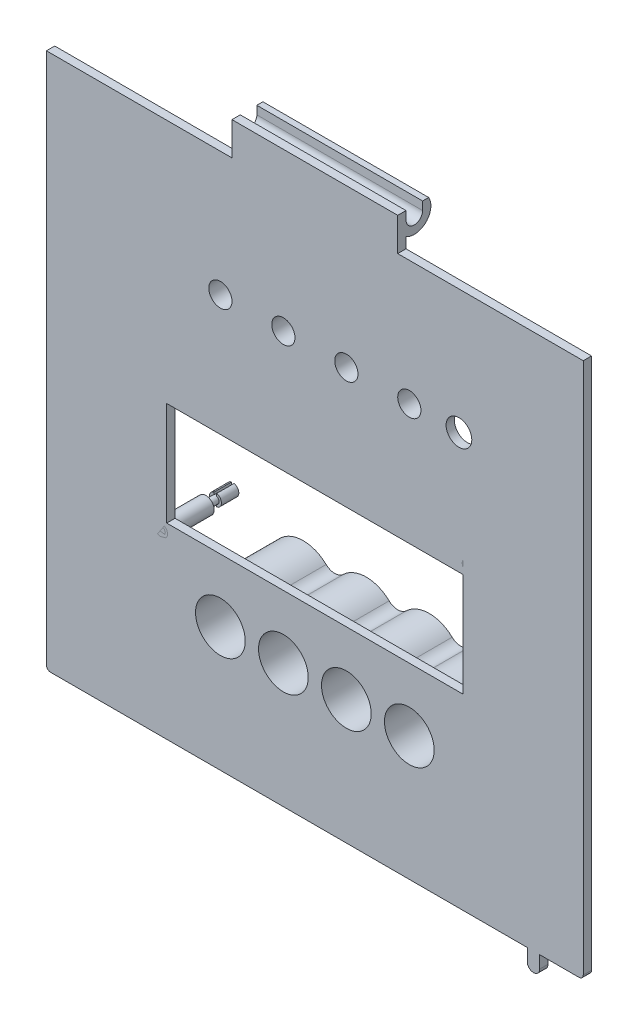
SolidWorks part; units mm, degrees
note: The reader was unsure of these and kept them because the rebuilt part matched: shared geometry of "Sketch1<5>", "Sketch1<6>", "Sketch1<7>", "Sketch1<8>", "Sketch1<9>", "Sketch4<4>", "Sketch4<5>".
ref_plane "Alzado" through (0, 0, 0) normal (0, 0, 1) x (1, 0, 0)
ref_plane "Planta" through (0, 0, 0) normal (0, 1, 0) x (1, 0, 0)
ref_plane "Vista lateral" through (0, 0, 0) normal (1, 0, 0) x (0, 0, -1)
sketch "Sketch1" plane through (0, 0, 0) normal (0, 0, 1) x (1, 0, 0)
  line L1 (-64.775, 64.7) -> (64.775, 64.7)
  line L2 (-64.775, 64.7) -> (-64.775, -64.7)
  line L3 (-64.775, -64.7) -> (51.275, -64.7)
  line L4 (64.775, 64.7) -> (64.775, -64.7)
  line L5 (-64.775, 64.7) -> (64.775, -64.7) construction
  line L6 (-64.775, -64.7) -> (64.775, 64.7) construction
  line L7 (36.7, 9.2186) -> (36.7, 6.3814)
  line L8 (37.3, 9.2186) -> (37.3, 6.3814)
  line L11 (36.7, -20.2814) -> (36.7, -23.1186)
  line L12 (0, 64.7) -> (0, -64.7) construction
  line L13 (37.3, -20.2814) -> (37.3, -23.1186)
  line L14 (-22.8, -34.7) -> (22.8, -34.7) construction
  line L15 (54.275, -64.7) -> (64.775, -64.7)
  line L16 (-20, 64.7) -> (20, 64.7)
  line L19 (-20, 64.7) -> (-20, 72.7)
  line L21 (-39, 9.8) -> (-39, -23.7) construction
  line L22 (-40, 11) -> (40, 11) construction
  line L23 (-40, 11) -> (-40, -25) construction
  line L24 (-40, -25) -> (40, -25) construction
  line L25 (40, 11) -> (40, -25) construction
  line L26 (-40, 11) -> (40, -25) construction
  line L27 (-40, -25) -> (40, 11) construction
  line L28 (-39, -23.7) -> (39, -23.7) construction
  line L29 (39, 9.8) -> (39, -23.7) construction
  line L30 (-39, 9.8) -> (39, 9.8) construction
  line L31 (-64.775, 0) -> (64.775, 0) construction
  line L32 (-35.75, 5.5) -> (35.75, 5.5)
  line L33 (-35.75, 5.5) -> (-35.75, -19.5)
  line L34 (-35.75, -19.5) -> (35.75, -19.5)
  line L35 (35.75, 5.5) -> (35.75, -19.5)
  line L36 (-35.75, 5.5) -> (35.75, -19.5) construction
  line L37 (-35.75, -19.5) -> (35.75, 5.5) construction
  line L42 (-20, 72.7) -> (20, 72.7)
  line L43 (20, 64.7) -> (20, 72.7)
  line L44 (-20, 64.7) -> (20, 72.7) construction
  line L45 (-20, 72.7) -> (20, 64.7) construction
  line L47 (51.275, -67.7) -> (51.275, -64.7)
  line L49 (54.275, -67.7) -> (54.275, -64.7)
  line L50 (51.275, -67.7) -> (54.275, -64.7) construction
  line L51 (51.275, -64.7) -> (54.275, -67.7) construction
  line L62 (-37.3, 9.2186) -> (-37.3, 6.3814)
  line L63 (-36.7, 9.2186) -> (-36.7, 6.3814)
  line L64 (-37.3, -20.2814) -> (-37.3, -23.1186)
  line L65 (-36.7, -20.2814) -> (-36.7, -23.1186)
  circle A4 centre (-22.8, -34.7) radius 4
  circle A5 centre (-7.6, -34.7) radius 4
  circle A6 centre (7.6, -34.7) radius 4
  circle A7 centre (22.8, -34.7) radius 4
  circle A12 centre (-37, 7.8) radius 2
  circle A13 centre (-37, -21.7) radius 2
  circle A14 centre (37, 7.8) radius 2
  circle A15 centre (37, -21.7) radius 2
  circle A16 centre (-22.8, -34.7) radius 6
  circle A17 centre (-7.6, -34.7) radius 6
  circle A18 centre (7.6, -34.7) radius 6
  circle A19 centre (22.8, -34.7) radius 6
  arc A20 (-17.2727, -28.9165) -> (-17.2727, -40.4835) centre (-22.8, -34.7) ccw
  arc A21 (-13.1273, -40.4835) -> (-2.0727, -40.4835) centre (-7.6, -34.7) ccw
  arc A22 (2.0727, -40.4835) -> (13.1273, -40.4835) centre (7.6, -34.7) ccw
  arc A23 (17.2727, -40.4835) -> (17.2727, -28.9165) centre (22.8, -34.7) ccw
  arc A24 (-2.0727, -28.9165) -> (-13.1273, -28.9165) centre (-7.6, -34.7) ccw
  arc A25 (17.2727, -40.4835) -> (13.1273, -40.4835) centre (15.2, -42.6524) ccw
  arc A26 (13.1273, -28.9165) -> (2.0727, -28.9165) centre (7.6, -34.7) ccw
  arc A27 (17.2727, -28.9165) -> (13.1273, -28.9165) centre (15.2, -26.7476) cw
  arc A28 (2.0727, -28.9165) -> (-2.0727, -28.9165) centre (0, -26.7476) cw
  arc A29 (-2.0727, -40.4835) -> (2.0727, -40.4835) centre (0, -42.6524) cw
  arc A30 (-13.1273, -40.4835) -> (-17.2727, -40.4835) centre (-15.2, -42.6524) ccw
  arc A31 (-13.1273, -28.9165) -> (-17.2727, -28.9165) centre (-15.2, -26.7476) cw
  arc A32 (51.275, -67.7) -> (54.275, -67.7) centre (52.775, -67.7) ccw
  circle A63 centre (37, -21.7) radius 1.45
  circle A64 centre (37, -21.7) radius 0.9
  circle A65 centre (37, 7.8) radius 1.45
  circle A66 centre (37, 7.8) radius 0.9
  circle A67 centre (-37, 7.8) radius 1.45
  circle A68 centre (-37, 7.8) radius 0.9
  circle A69 centre (-37, -21.7) radius 1.45
  circle A70 centre (-37, -21.7) radius 0.9
  point P0 (0, 0)
  point P19 (52.775, -66.2)
  point P48 (0, 68.7)
  point P52 (0, -34.7)
  point P58 (0, -7)
  point P85 (0, -7)
  dimension "D4" = 0.6
  dimension "D5" = 2.9
  dimension "D6" = 8
  dimension "D10" = 4
  dimension "D11" = 1
  dimension "D13" = 8
  dimension "D14" = 12
  dimension "D15" = 1
  dimension "D16" = 3
  dimension "D37" = 41
  dimension "D7" = 1.8
  dimension "D22" = 3
  dimension "D23" = 3
  dimension "D1" = 5.5
  dimension "D2" = 129.55
  dimension "D3" = 129.4
  dimension "D8" = 25
  dimension "D9" = 71.5
  dimension "D12" = 1.3
  dimension "D17" = 33.5
  dimension "D18" = 15.2
  dimension "D19" = 30
  dimension "D20" = 8
  dimension "D21" = 40
  dimension "D24" = 12
  dimension "D26" = 37
extrude "Boss-Extrude1" add sketch "Sketch1" against normal blind 2
extrude "Boss-Extrude3" add sketch "Sketch1<5>" against normal blind 20 contours A24 A31 A20 A30 A21 A29 A22 A25 A23 A27 A26 A28 A16 A17 A18 A19
sketch "Sketch1<5>" plane through (0, 0, 0) normal (0, 0, 1) x (1, 0, 0) same geometry as "Sketch1"
extrude "Boss-Extrude4" add sketch "Sketch1<6>" along normal blind 2 from surface at -20 contours A19 A7 | A18 A6 | A17 A5 | A16 A4 starting at face at (-16.8, -34.7, -20)
sketch "Sketch1<6>" plane through (0, 0, 0) normal (0, 0, 1) x (1, 0, 0) same geometry as "Sketch1"
extrude "Boss-Extrude5" add sketch "Sketch1<7>" against normal blind 10.7 contours A12 A67 | A13 A69 | A15 A63 | A14 A65
sketch "Sketch1<7>" plane through (0, 0, 0) normal (0, 0, 1) x (1, 0, 0) same geometry as "Sketch1"
extrude "Boss-Extrude6" add sketch "Sketch1<8>" against normal blind 14.2 separate body
sketch "Sketch1<8>" plane through (0, 0, 0) normal (0, 0, 1) x (1, 0, 0) same geometry as "Sketch1"
extrude "Boss-Extrude7" add sketch "Sketch1<9>" against normal blind 3 and the other way blind 1.2 from surface at -14.2
sketch "Sketch1<9>" plane through (0, 0, 0) normal (0, 0, 1) x (1, 0, 0) same geometry as "Sketch1"
sketch "Sketch3" plane through (0, 0, -2) normal (0, 0, -1) x (-1, 0, 0)
  line L0 (-64.775, 64.7) -> (-64.775, -64.7) construction
  line L1 (64.775, 64.7) -> (20, 64.7) construction
  circle A0 centre (-34.775, 34.7) radius 3.1
  dimension "D3" = 6.2
  dimension "D1" = 30
  dimension "D2" = 30
extrude "Cut-Extrude1" cut sketch "Sketch3" against normal blind 4.2
sketch "Sketch4" plane through (0, 0, 0) normal (0, 0, 1) x (1, 0, 0)
  line L0 (-22.8, 34.7) -> (22.8, 34.7) construction
  line L1 (-25.293, 35.9748) -> (-20.307, 35.9748)
  line L2 (-25.293, 33.4252) -> (-20.307, 33.4252)
  line L3 (5.107, 35.9748) -> (10.093, 35.9748)
  line L4 (5.107, 33.4252) -> (10.093, 33.4252)
  line L5 (20.307, 33.4252) -> (25.293, 33.4252)
  line L6 (20.307, 35.9748) -> (25.293, 35.9748)
  line L7 (-10.093, 33.4252) -> (-5.107, 33.4252)
  line L8 (-10.093, 35.9748) -> (-5.107, 35.9748)
  line L9 (-64.775, 64.7) -> (-20, 64.7) construction
  circle A0 centre (22.8, -34.7) radius 6 construction
  circle A1 centre (7.6, -34.7) radius 6 construction
  circle A2 centre (-7.6, -34.7) radius 6 construction
  circle A3 centre (-22.8, -34.7) radius 6 construction
  circle A4 centre (22.8, -34.7) radius 6
  circle A5 centre (7.6, -34.7) radius 6
  circle A6 centre (-7.6, -34.7) radius 6
  circle A7 centre (-22.8, -34.7) radius 6
  circle A8 centre (-22.8, 34.7) radius 2.8
  circle A9 centre (-7.6, 34.7) radius 2.8
  circle A10 centre (7.6, 34.7) radius 2.8
  circle A11 centre (22.8, 34.7) radius 2.8
  circle A12 centre (-22.8, 34.7) radius 4.8
  circle A13 centre (-7.6, 34.7) radius 4.8
  circle A14 centre (7.6, 34.7) radius 4.8
  circle A15 centre (22.8, 34.7) radius 4.8
  dimension "D2" = 5.6
  dimension "D3" = 2.5496
  dimension "D4" = 30
  dimension "D5" = 2
  dimension "D1" = 4
extrude "Boss-Extrude8" add sketch "Sketch4" against normal blind 11 contours A12 | A13 | A14 | A15
extrude "Cut-Extrude2" cut sketch "Sketch4<4>" against normal blind 10 contours L1 A8 | L2 A8 | L7 A9 | L8 A9 | L3 A10 | L4 A10 | L5 A11 | L6 A11
sketch "Sketch4<4>" plane through (0, 0, 0) normal (0, 0, 1) x (1, 0, 0) same geometry as "Sketch4"
extrude "Cut-Extrude3" cut sketch "Sketch4<5>" against normal blind 19
sketch "Sketch4<5>" plane through (0, 0, 0) normal (0, 0, 1) x (1, 0, 0) same geometry as "Sketch4"
sketch "Sketch6" plane through (-20, 0, 0) normal (-1, 0, 0) x (0, 0, 1)
  line L1 (-2, 64.7) -> (-2, 72.7) construction
  line L3 (-8, 70.7) -> (0, 70.7) construction
  line L4 (0, 64.7) -> (0, 72.7) construction
  line L5 (-2, 72.7) -> (0, 72.7) construction
  line L7 (-7.4641, 72.7) -> (-6, 72.7)
  line L8 (-6, 72.7) -> (-6, 70.7)
  arc A0 (-6, 70.7) -> (-2, 70.7) centre (-4, 70.7) ccw
  arc A1 (-7.4641, 72.7) -> (0, 70.7) centre (-4, 70.7) ccw
  line M9 (-2, 72.7) -> (-2, 64.7)
  dimension "D2" = 2
  dimension "D1" = 2
extrude "Boss-Extrude9" add sketch "Sketch6" against normal blind 40 contours L3 A1 A0 M9 | A1 L3 L8 L7
fillet "Fillet1" radius 1 2 edges at (64.775, -64.7, -1) (-64.775, -64.7, -1)
